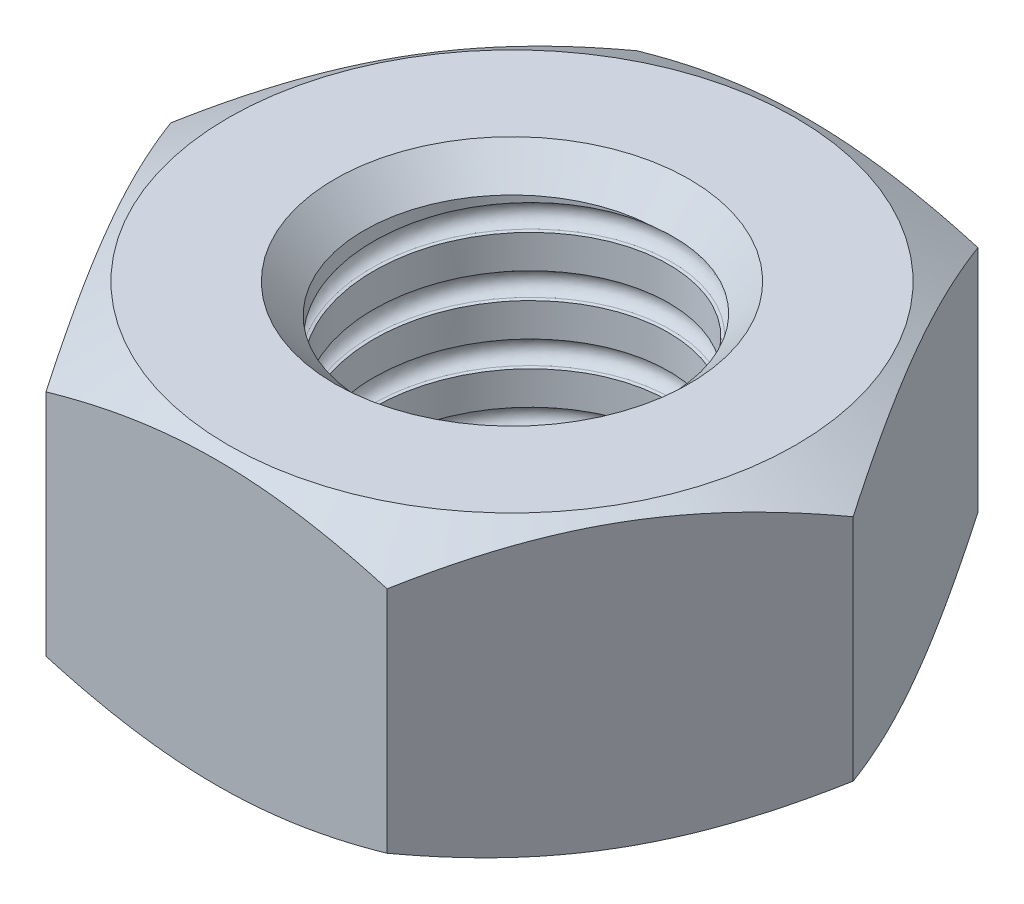
SolidWorks part; units mm, degrees
ref_plane "Спереди" through (0, 0, 0) normal (0, 0, 1) x (1, 0, 0)
ref_plane "Сверху" through (0, 0, 0) normal (0, 1, 0) x (1, 0, 0)
ref_plane "Справа" through (0, 0, 0) normal (1, 0, 0) x (0, 0, -1)
sketch "Эскиз1" plane through (0, 0, 0) normal (0, 1, 0) x (1, 0, 0)
  line L1 (5.7735, 0) -> (2.8868, 5)
  line L2 (2.8868, 5) -> (-2.8868, 5)
  line L3 (-2.8868, 5) -> (-5.7735, 0)
  line L4 (-5.7735, 0) -> (-2.8868, -5)
  line L5 (-2.8868, -5) -> (2.8868, -5)
  line L6 (2.8868, -5) -> (5.7735, 0)
  circle A0 centre (0, 0) radius 5 construction
  dimension "D1" = 10
extrude "Бобышка-Вытянуть1" add sketch "Эскиз1" along normal blind 5
sketch "Эскиз2" plane through (0, 5, 0) normal (0, 1, 0) x (1, 0, 0)
  circle A0 centre (0, 0) radius 4.8
  dimension "D1" = 9.6
extrude "Вырез-Вытянуть7" cut sketch "Эскиз2" against normal blind 3 draft 60 flip side to cut
sketch "Эскиз3" plane through (0, 0, 0) normal (0, -1, 0) x (1, 0, 0)
  circle A0 centre (0, 0) radius 4.8
  dimension "D1" = 9.6
extrude "Вырез-Вытянуть8" cut sketch "Эскиз3" against normal blind 3 draft 60 flip side to cut
sketch "Эскиз4" plane through (0, 0, 0) normal (0, -1, 0) x (1, 0, 0)
  circle A0 centre (0, 0) radius 2.5
  dimension "D1" = 5
extrude "Вырез-Вытянуть9" cut sketch "Эскиз4" against normal blind 5
chamfer "Фаска1" distance 0.5 angle 45 2 edges at (0, 5, -2.5) (0, 0, -2.5)
sketch "Эскиз5" plane through (0, 0, 0) normal (0, 0, 1) x (1, 0, 0)
  line L0 (-2.0944, 3.4046) -> (-2.0944, 2.6721)
  line L1 (-2.0944, 2.6721) -> (-2.5449, 2.8361)
  line L2 (-2.5449, 3.2407) -> (-2.0944, 3.4046)
  line L3 (-2.0944, 3.0384) -> (-2.6866, 3.0384) construction
  arc A0 (-2.5449, 3.2407) -> (-2.5449, 2.8361) centre (-2.4713, 3.0384) ccw
  dimension "D1" = 40
sketch "Эскиз6" plane through (0, 0, 0) normal (0, 1, 0) x (1, 0, 0)
  circle A0 centre (0, 0) radius 2.5
  dimension "D1" = 5
curve "Спираль1" pitch 1 height 6 radius 2.5 left hand yes centre (0, 0, 0) axis (0, 1, 0) start towards (0, 0, 1)
sweep "Вырез-По траектории2" cut profiles "Эскиз5" path "Спираль1"
